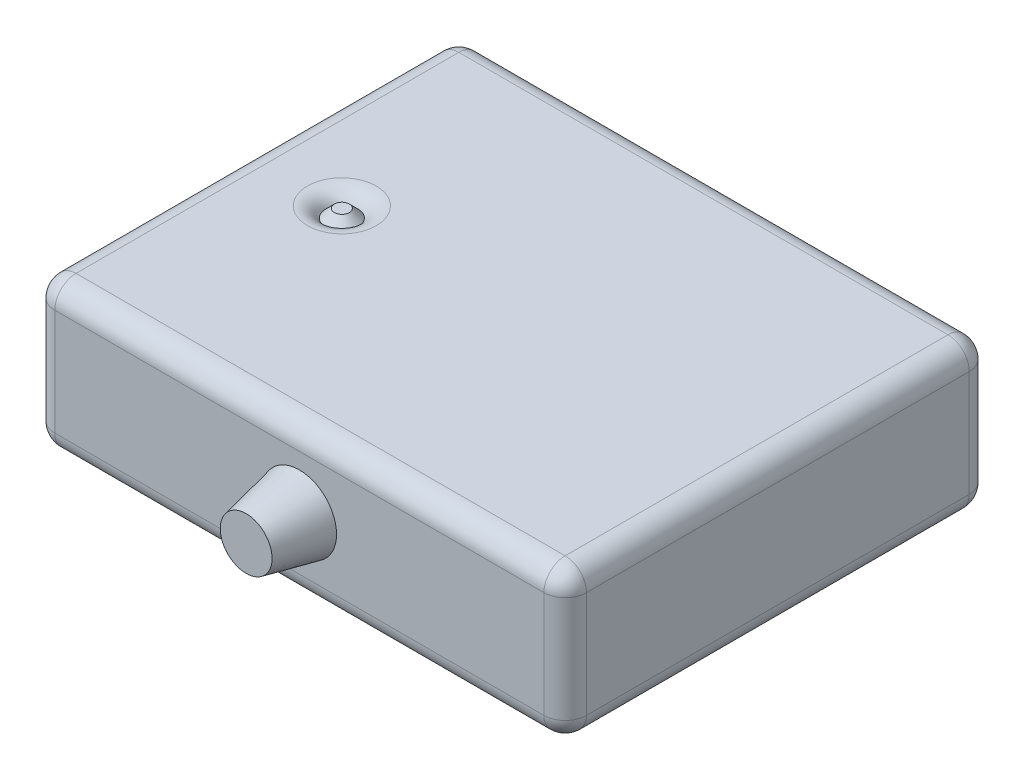
SolidWorks part; units mm, degrees
ref_plane "Front Plane" through (0, 0, 0) normal (0, 0, 1) x (1, 0, 0)
ref_plane "Top Plane" through (0, 0, 0) normal (0, 1, 0) x (1, 0, 0)
ref_plane "Right Plane" through (0, 0, 0) normal (1, 0, 0) x (0, 0, -1)
sketch "Sketch1" plane through (0, 0, 0) normal (0, 1, 0) x (1, 0, 0)
  line L1 (-31.75, 25.4) -> (31.75, 25.4)
  line L2 (-31.75, 25.4) -> (-31.75, -25.4)
  line L3 (-31.75, -25.4) -> (31.75, -25.4)
  line L4 (31.75, 25.4) -> (31.75, -25.4)
  line L5 (-31.75, 25.4) -> (31.75, -25.4) construction
  line L6 (-31.75, -25.4) -> (31.75, 25.4) construction
  point P0 (0, 0)
  dimension "D1" = 63.5
  dimension "D2" = 50.8
extrude "Boss-Extrude1" add sketch "Sketch1" along normal blind 17.78
sketch "Sketch2" plane through (0, 0, 25.4) normal (0, 0, 1) x (1, 0, 0)
  line L0 (-31.75, 8.89) -> (31.75, 8.89) construction
  line L1 (-31.75, 17.78) -> (-31.75, 0) construction
  line L2 (31.75, 17.78) -> (31.75, 0) construction
  circle A0 centre (0, 8.89) radius 4.445
  dimension "D1" = 8.89
extrude "Boss-Extrude2" add sketch "Sketch2" along normal blind 6.35 draft 12 separate body
sketch "Sketch3" plane through (0, 17.78, 0) normal (0, 1, 0) x (1, 0, 0)
  line L0 (-20.32, -25.4) -> (-20.32, 25.4) construction
  line L1 (-31.75, -25.4) -> (31.75, -25.4) construction
  line L2 (31.75, 25.4) -> (-31.75, 25.4) construction
  line L3 (-31.75, 25.4) -> (-31.75, -25.4) construction
  circle A0 centre (-20.32, 0) radius 1.905
  dimension "D2" = 3.81
  dimension "D1" = 11.43
extrude "Cut-Extrude1" cut sketch "Sketch3" against normal blind 1.27
sketch "Sketch4" plane through (0, 16.51, 0) normal (0, 1, 0) x (1, 0, 0)
  circle A0 centre (-20.32, 0) radius 1.905
extrude "Boss-Extrude3" add sketch "Sketch4" along normal blind 1.016 draft 45
fillet "Fillet1" radius 2.54 5 edges at (0, 17.78, 25.4) (-31.75, 17.78, 0) (31.75, 17.78, 0) (0, 17.78, -25.4) (-20.32, 17.78, 1.905) tangent propagation no
fillet "Fillet2" radius 2.54 12 edges at (-31.0061, 17.0361, 24.6561) (31.0061, 17.0361, 24.6561) (31.0061, 17.0361, -24.6561) (-31.0061, 17.0361, -24.6561) (0, 0, 25.4) (-31.75, 0, 0) (-31.75, 7.62, 25.4) (31.75, 0, 0) (31.75, 7.62, 25.4) (0, 0, -25.4) (31.75, 7.62, -25.4) (-31.75, 7.62, -25.4)
